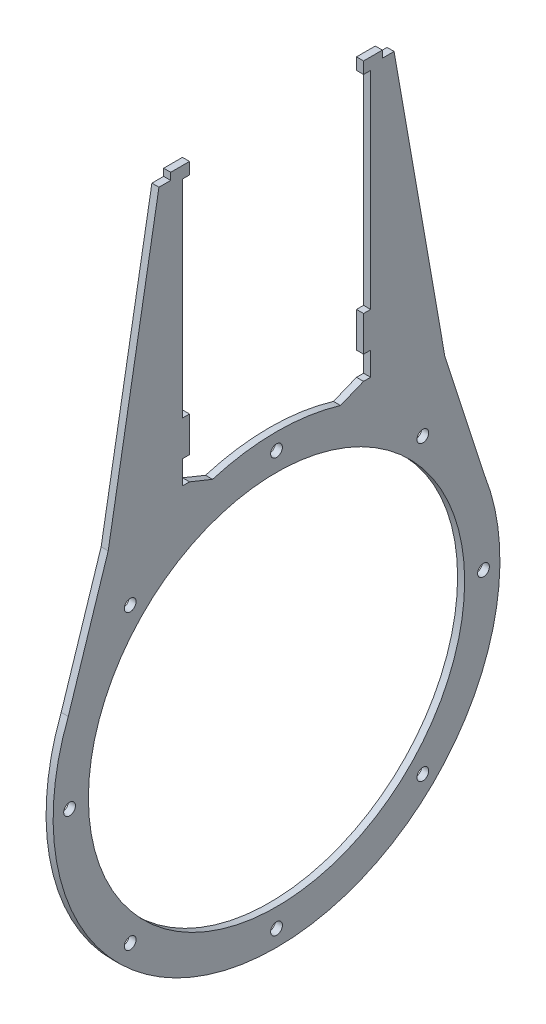
SolidWorks part; units mm, degrees
material "201 Stal nierdzewna odprężona (SS)"
ref_plane "Płaszczyzna przednia" through (0, 0, 0) normal (0, 0, 1) x (1, 0, 0)
ref_plane "Płaszczyzna górna" through (0, 0, 0) normal (0, 1, 0) x (1, 0, 0)
ref_plane "Płaszczyzna prawa" through (0, 0, 0) normal (1, 0, 0) x (0, 0, -1)
sketch "Szkic1" plane through (0, 0, 0) normal (1, 0, 0) x (0, 0, -1)
  line L0 (37, 213) -> (45, 213)
  line L2 (45, 213) -> (45, 210)
  line L3 (45, 210) -> (50, 210)
  line L4 (37, 120) -> (37, 105)
  line L5 (37, 105) -> (40, 105)
  line L6 (40, 105) -> (40, 95)
  line L7 (37, 120) -> (40, 120)
  line L8 (40, 120) -> (40, 208)
  line L11 (40, 95) -> (37, 95)
  line L12 (37, 95) -> (27.1941, 91.0246)
  line L13 (-37, 120) -> (-37, 105)
  line L14 (-37, 105) -> (-40, 105)
  line L15 (-40, 105) -> (-40, 95)
  line L16 (-37, 120) -> (-40, 120)
  line L17 (-40, 120) -> (-40, 208)
  line L19 (-40, 95) -> (-37, 95)
  line L20 (-37, 95) -> (-27.1941, 91.0246)
  line L21 (50, 210) -> (71.5824, 86.8702)
  line L22 (71.5824, 86.8702) -> (88.5602, 34.3816)
  line L23 (-71.5824, 86.8702) -> (-88.5602, 34.3816)
  line L24 (37, 213) -> (37, 208)
  line L25 (37, 208) -> (40, 208)
  line L26 (-37, 213) -> (-45, 213)
  line L28 (-45, 213) -> (-45, 210)
  line L29 (-45, 210) -> (-50, 210)
  line L31 (-50, 210) -> (-71.5824, 86.8702)
  line L32 (-37, 213) -> (-37, 208)
  line L33 (-37, 208) -> (-40, 208)
  circle A0 centre (0, 0) radius 80
  circle A1 centre (0, 88) radius 2.5
  circle A2 centre (-62.2254, 62.2254) radius 2.5
  circle A3 centre (-88, 0) radius 2.5
  circle A4 centre (-62.2254, -62.2254) radius 2.5
  circle A5 centre (0, -88) radius 2.5
  circle A6 centre (62.2254, -62.2254) radius 2.5
  circle A7 centre (88, 0) radius 2.5
  circle A8 centre (62.2254, 62.2254) radius 2.5
  arc A9 (27.1941, 91.0246) -> (-27.1941, 91.0246) centre (0, 0) ccw
  arc A10 (-88.5602, 34.3816) -> (88.5602, 34.3816) centre (0, 0) ccw
extrude "Dodanie-wyciągnięcie1" add sketch "Szkic1" along normal blind 3
